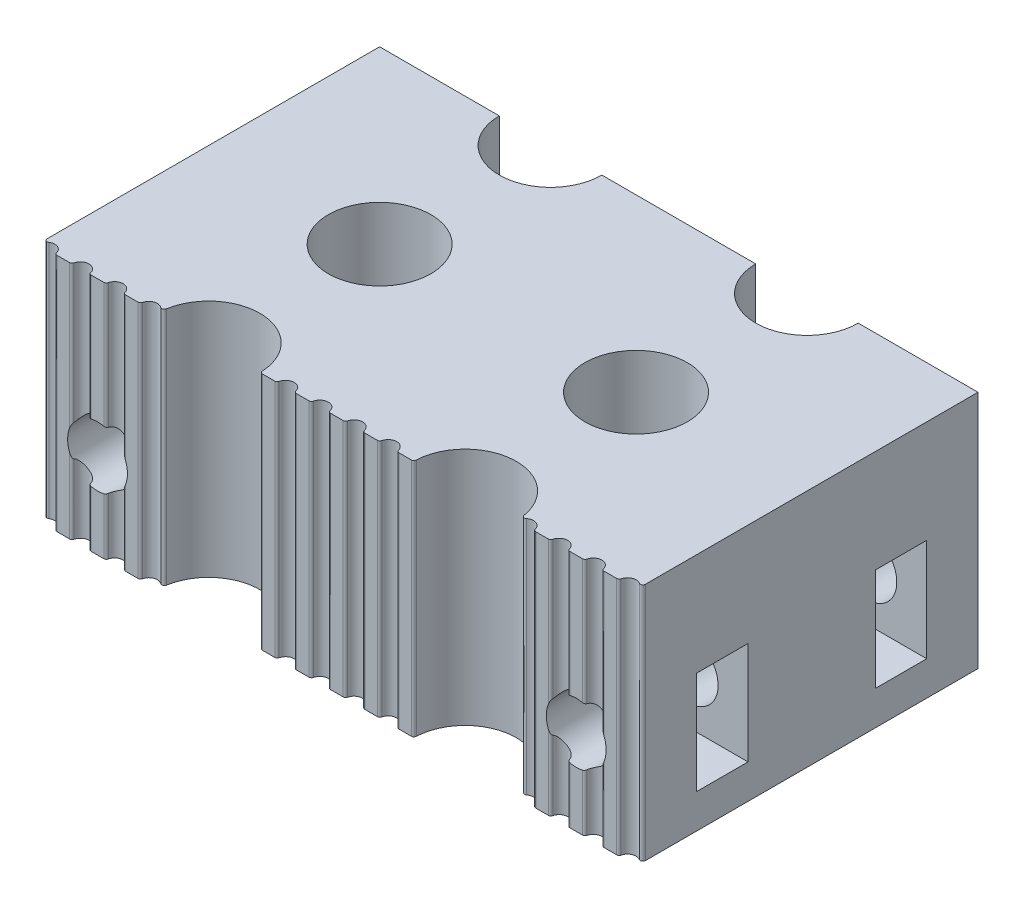
SolidWorks part; units mm, degrees
material "ABS"
ref_plane "Front Plane" through (0, 0, 0) normal (0, 0, 1) x (1, 0, 0)
ref_plane "Top Plane" through (0, 0, 0) normal (0, 1, 0) x (1, 0, 0)
ref_plane "Right Plane" through (0, 0, 0) normal (1, 0, 0) x (0, 0, -1)
sketch "Sketch1" plane through (0, 0, 0) normal (0, 1, 0) x (1, 0, 0)
  line L5 (-17.5, 10) -> (17.5, 10)
  line L6 (-17.5, 10) -> (-17.5, -10)
  line L7 (-17.5, -10) -> (17.5, -10)
  line L8 (17.5, 10) -> (17.5, -10)
  line L9 (-17.5, 10) -> (17.5, -10) construction
  line L10 (-17.5, -10) -> (17.5, 10) construction
  point P0 (0, 0)
  dimension "D1" = 35
  dimension "D2" = 20
extrude "Boss-Extrude1" add sketch "Sketch1" along normal blind 14
sketch "Sketch2" plane through (0, 14, 0) normal (0, 1, 0) x (1, 0, 0)
  line L0 (-17.5, -10) -> (17.5, -10) construction
  line L1 (-17.5, 10) -> (-17.5, -10) construction
  line L2 (17.5, -10) -> (17.5, 10) construction
  line L3 (17.5, 10) -> (-17.5, 10) construction
  circle A0 centre (-7.5, -10) radius 3
  circle A1 centre (7.5, -10) radius 3
  circle A2 centre (-7.5, 10) radius 3
  circle A3 centre (7.5, 10) radius 3
  dimension "D1" = 6
  dimension "D3" = 6
  dimension "D5" = 6
  dimension "D6" = 6
  dimension "D2" = 10
  dimension "D4" = 10
extrude "Cut-Extrude1" cut sketch "Sketch2" against normal blind 14
sketch "Sketch3" plane through (0, 14, 0) normal (0, 1, 0) x (1, 0, 0)
  line L0 (-17.5, -10) -> (-10.5, -10) construction
  circle A0 centre (-17, -10) radius 0.5
  dimension "D1" = 1
extrude "Cut-Extrude2" cut sketch "Sketch3" against normal blind 14
pattern_linear "LPattern1" count 18 spacing 2 along (1, 0, 0) of "Cut-Extrude2"
fillet "Fillet1" radius 0.15 26 edges at (-10.5, 7, 10) (-11.5, 7, 10) (-12.5, 7, 10) (-13.5, 7, 10) (-14.5, 7, 10) (-15.5, 7, 10) (-16.5, 7, 10) (-17.5, 7, 10) (17.5, 7, 10) (16.5, 7, 10) (15.5, 7, 10) (14.5, 7, 10) (13.5, 7, 10) (12.5, 7, 10) (11.5, 7, 10) (10.5, 7, 10) (4.5, 7, 10) (3.5, 7, 10) (2.5, 7, 10) (1.5, 7, 10) (0.5, 7, 10) (-0.5, 7, 10) (-1.5, 7, 10) (-2.5, 7, 10) (-3.5, 7, 10) (-4.5, 7, 10)
sketch "Sketch5" plane through (0, 14, 0) normal (0, 1, 0) x (1, 0, 0)
  line L0 (17.5, -9.4523) -> (17.5, 10) construction
  line L1 (-17.5, 10) -> (-17.5, -9.4523) construction
  circle A0 centre (-7.5, 0) radius 1.75
  circle A1 centre (7.5, 0) radius 1.75
  dimension "D1" = 3.5
  dimension "D2" = 3.5
  dimension "D3" = 10
  dimension "D4" = 10
extrude "Cut-Extrude4" cut sketch "Sketch5" against normal through all
sketch "Sketch7" plane through (0, 0, -10) normal (0, 0, -1) x (-1, 0, 0)
  line L0 (-17.5, 0) -> (-10.5, 0) construction
  line L2 (-17.5, 14) -> (-17.5, 0) construction
  line L3 (17.5, 14) -> (17.5, 0) construction
  line L4 (10.5, 0) -> (17.5, 0) construction
  circle A0 centre (-14, 5) radius 1.75
  circle A1 centre (14, 5) radius 1.75
  dimension "D3" = 3.5
  dimension "D4" = 3.5
  dimension "D1" = 5
  dimension "D2" = 3.5
  dimension "D5" = 3.5
  dimension "D6" = 5
extrude "Cut-Extrude5" cut sketch "Sketch7" against normal through all
sketch "Sketch8" plane through (0, 14, 0) normal (0, 1, 0) x (1, 0, 0)
  circle A0 centre (7.5, 0) radius 3
  circle A1 centre (-7.5, 0) radius 3
  dimension "D1" = 6
  dimension "D2" = 6
extrude "Cut-Extrude6" cut sketch "Sketch8" against normal blind 5
sketch "Sketch9" plane through (17.5, 0, 0) normal (1, 0, 0) x (0, 0, -1)
  line L0 (10, 14) -> (10, 0) construction
  line L1 (4, 8) -> (7, 8)
  line L2 (4, 8) -> (4, 2)
  line L3 (4, 2) -> (7, 2)
  line L4 (7, 8) -> (7, 2)
  line L5 (-9.4523, 14) -> (-9.4523, 0) construction
  line L6 (-6.4523, 8) -> (-3.4523, 8)
  line L7 (-6.4523, 8) -> (-6.4523, 2)
  line L8 (-6.4523, 2) -> (-3.4523, 2)
  line L9 (-3.4523, 8) -> (-3.4523, 2)
  line L10 (-9.4523, 0) -> (10, 0) construction
  dimension "D1" = 6
  dimension "D2" = 3
  dimension "D3" = 3
  dimension "D4" = 3
  dimension "D5" = 3
  dimension "D6" = 2
  dimension "D7" = 6
  dimension "D8" = 2
extrude "Cut-Extrude7" cut sketch "Sketch9" against normal blind 7
sketch "Sketch10" plane through (-17.5, 0, 0) normal (-1, 0, 0) x (0, 0, 1)
  line L0 (-10, 0) -> (9.4523, 0) construction
  line L1 (3.4523, 8) -> (6.4523, 8)
  line L2 (3.4523, 8) -> (3.4523, 2)
  line L3 (3.4523, 2) -> (6.4523, 2)
  line L4 (6.4523, 8) -> (6.4523, 2)
  line L5 (9.4523, 0) -> (9.4523, 14) construction
  line L6 (-10, 14) -> (-10, 0) construction
  line L7 (-7, 8) -> (-4, 8)
  line L8 (-7, 8) -> (-7, 2)
  line L9 (-7, 2) -> (-4, 2)
  line L10 (-4, 8) -> (-4, 2)
  dimension "D1" = 3
  dimension "D2" = 6
  dimension "D3" = 2
  dimension "D4" = 3
  dimension "D5" = 3
  dimension "D6" = 3
extrude "Cut-Extrude8" cut sketch "Sketch10" against normal blind 7
